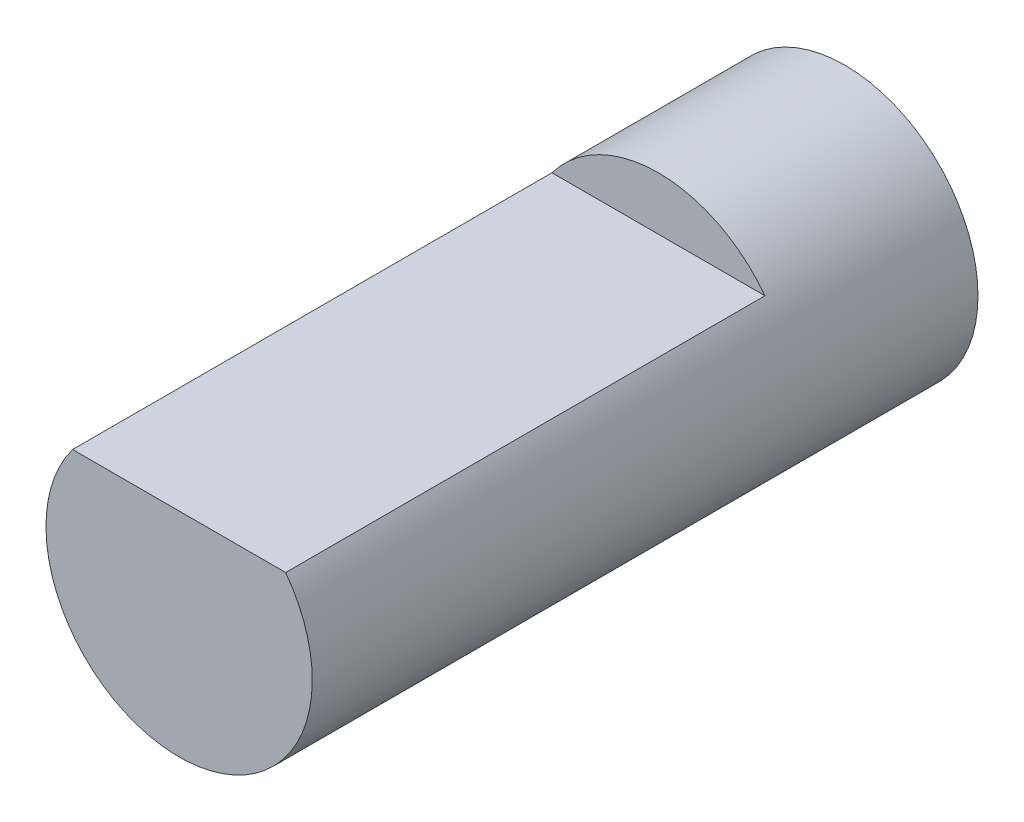
SolidWorks part; units mm, degrees
ref_plane "Piano frontale" through (0, 0, 0) normal (0, 0, 1) x (1, 0, 0)
ref_plane "Piano superiore" through (0, 0, 0) normal (0, 1, 0) x (1, 0, 0)
ref_plane "Piano destro" through (0, 0, 0) normal (1, 0, 0) x (0, 0, -1)
sketch "Sketch1" plane through (0, 0, 0) normal (0, 0, 1) x (1, 0, 0)
  circle A0 centre (0, 0) radius 2.5
extrude "Boss-Extrude2" add sketch "Sketch1" along normal blind 3.5
sketch "Sketch3" plane through (0, 0, 3.5) normal (0, 0, 1) x (1, 0, 0)
  line L1 (-2, 1.5) -> (2, 1.5)
  circle A0 centre (0, 0) radius 2.5 construction
  arc A1 (-2, 1.5) -> (2, 1.5) centre (0, 0) ccw
extrude "Boss-Extrude3" add sketch "Sketch3" along normal blind 9
